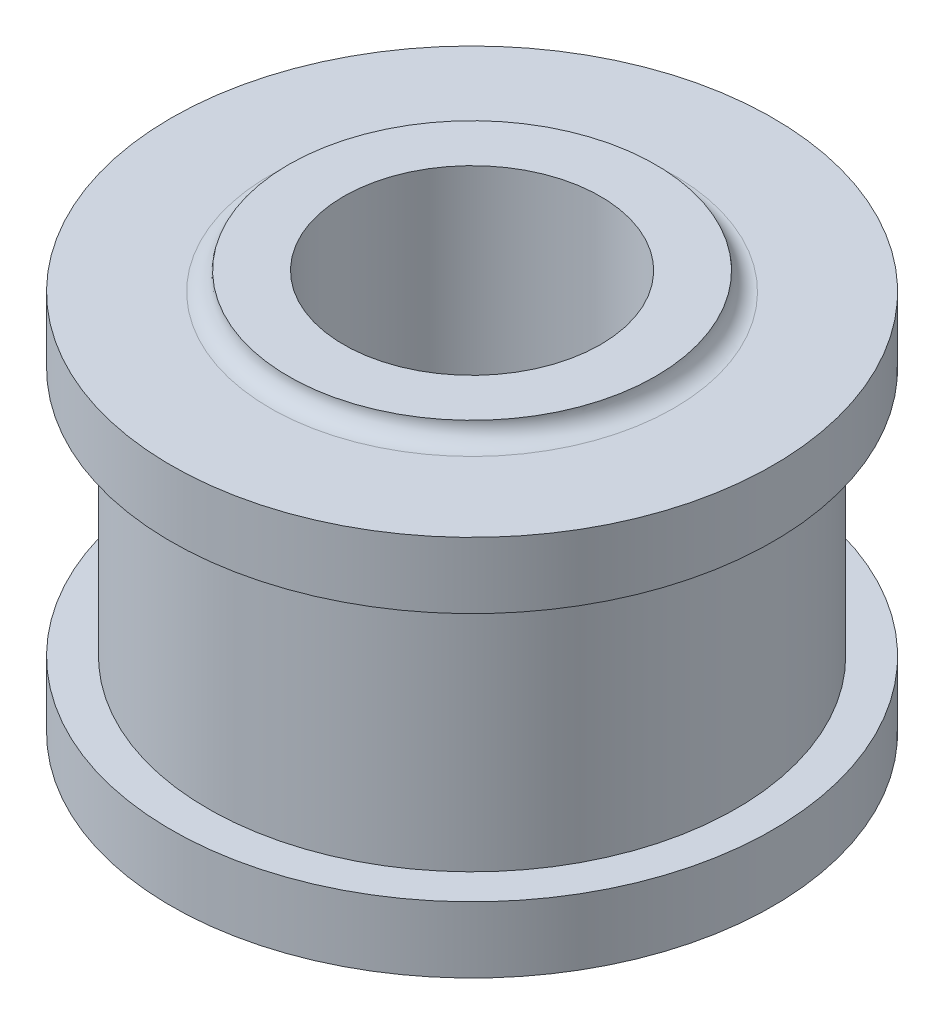
SolidWorks part; units mm, degrees
material "1.0036 (S235JRG1)"
ref_plane "Front Plane" through (0, 0, 0) normal (0, 0, 1) x (1, 0, 0)
ref_plane "Top Plane" through (0, 0, 0) normal (0, 1, 0) x (1, 0, 0)
ref_plane "Right Plane" through (0, 0, 0) normal (1, 0, 0) x (0, 0, -1)
sketch "Sketch1" plane through (0, 0, 0) normal (0, 0, 1) x (1, 0, 0)
  line L0 (0, 60.7377) -> (0, -60.7377) construction
  line L1 (0, 0) -> (25, 0)
  line L2 (25, 0) -> (25, 2.5)
  line L3 (25, 2.5) -> (41, 2.5)
  line L4 (41, 2.5) -> (41, 11.5)
  line L5 (41, 11.5) -> (36, 11.5)
  line L6 (36, 11.5) -> (36, 45.5)
  line L7 (36, 45.5) -> (41, 45.5)
  line L8 (41, 45.5) -> (41, 54.5)
  line L9 (41, 54.5) -> (25, 54.5)
  line L10 (25, 54.5) -> (25, 57)
  line L11 (25, 57) -> (0, 57)
  line L12 (0, 0) -> (0, 57)
  point P4 (0, 0)
  point P16 (0, 60.7377)
  point P18 (0, 57)
  dimension "D1" = 57
  dimension "D2" = 34
  dimension "D3" = 52
  dimension "D4" = 50
  dimension "D5" = 82
  dimension "D6" = 72
revolve "Revolve1" add sketch "Sketch1" angle 360 about L0
sketch "Sketch2" plane through (0, 57, 0) normal (0, 1, 0) x (1, 0, 0)
  circle A0 centre (0, 0) radius 17.5
  dimension "D1" = 35
extrude "Cut-Extrude1" cut sketch "Sketch2" against normal up to next
fillet "Fillet1" radius 2.5 2 edges at (-25, 2.5, 0) (-25, 54.5, 0)
